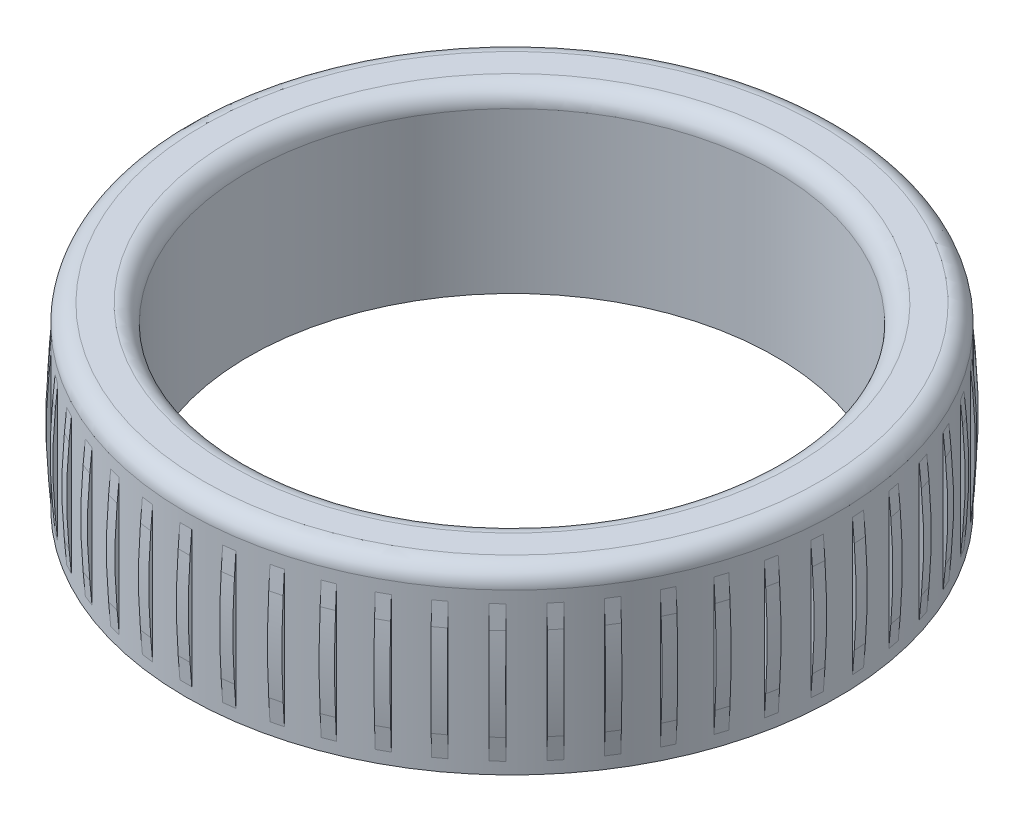
SolidWorks part; units mm, degrees
material "ABS"
ref_plane "Alzado" through (0, 0, 0) normal (0, 0, 1) x (1, 0, 0)
ref_plane "Planta" through (0, 0, 0) normal (0, 1, 0) x (1, 0, 0)
ref_plane "Vista lateral" through (0, 0, 0) normal (1, 0, 0) x (0, 0, -1)
sketch "Sketch1" plane through (0, 0, 0) normal (0, 1, 0) x (1, 0, 0)
  circle A0 centre (0, 0) radius 22.225
  circle A1 centre (0, 0) radius 27.5
  dimension "D1" = 44.45
  dimension "D2" = 55
extrude "Boss-Extrude1" add sketch "Sketch1" along normal blind 15
fillet "Fillet1" radius 1.5 2 edges at (0, 15, 27.5) (0, 15, 22.225)
sketch "Sketch2" plane through (0, 0, 0) normal (1, 0, 0) x (0, 0, -1)
  line L0 (27.5, 12.5) -> (27.95, 6.75)
  line L1 (27.5, 0) -> (27.5, 13.5) construction
  line L2 (27.95, 6.75) -> (27.5, 1)
  line L3 (27.5, 12.5) -> (27.5, 1)
  line L4 (-27.5, 0) -> (27.5, 0) construction
  line L5 (-27.5, 13.5) -> (27.5, 13.5) construction
  point P9 (27.5, 6.75)
  dimension "D1" = 1
  dimension "D2" = 1
  dimension "D3" = 0.45
extrude "Boss-Extrude2" add sketch "Sketch2" along normal blind 0.5 and the other way blind 0.5 separate body
fillet "Fillet2" radius 50 1 edges at (0, 6.75, -27.95) type face fillet first side face at (0, 9.625, -27.725) second side face at (0, 3.875, -27.725)
pattern_circular "CirPattern3" count 50 over 360 about axis through (0, 13.5, 0) along (0, -1, 0) of bodies 102
